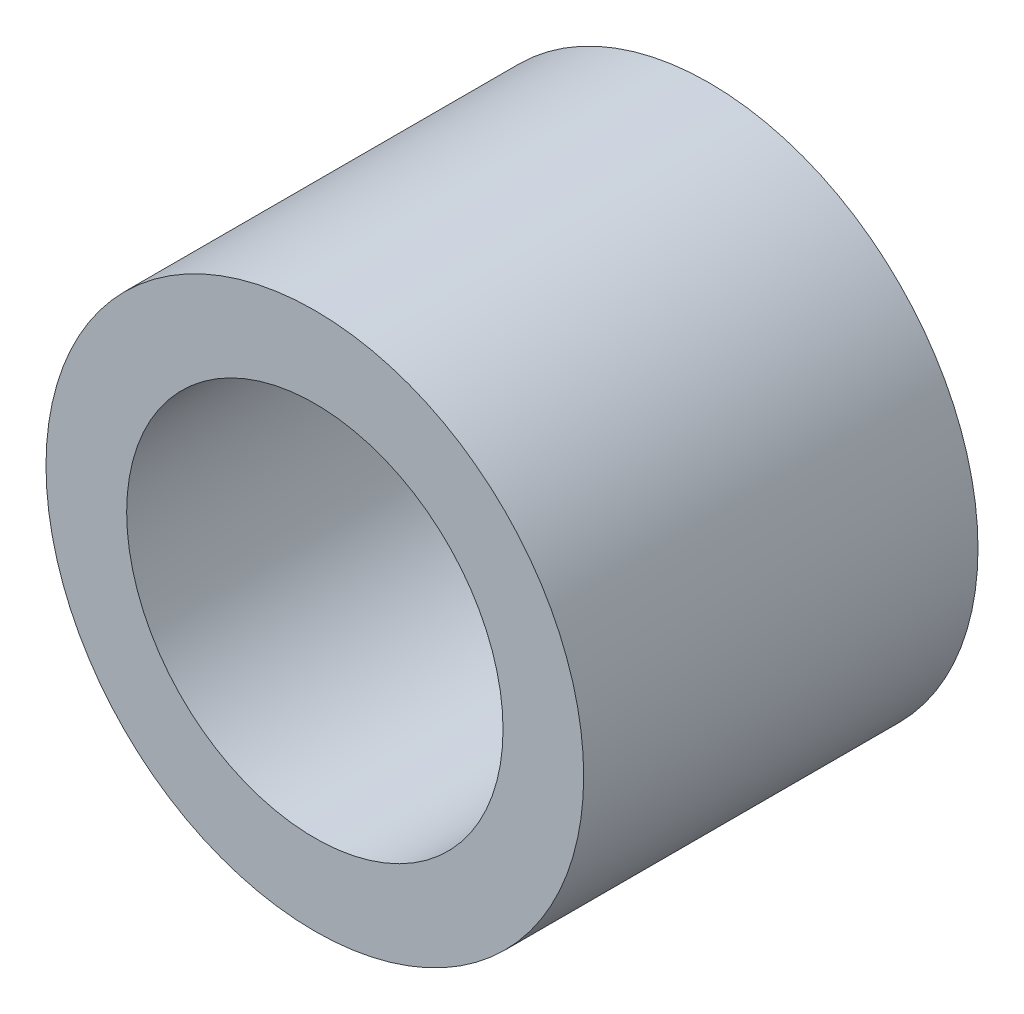
SolidWorks part; units mm, degrees
material "ABS"
ref_plane "Alzado" through (0, 0, 0) normal (0, 0, 1) x (1, 0, 0)
ref_plane "Planta" through (0, 0, 0) normal (0, 1, 0) x (1, 0, 0)
ref_plane "Vista lateral" through (0, 0, 0) normal (1, 0, 0) x (0, 0, -1)
sketch "Croquis1" plane through (0, 0, 0) normal (0, 0, 1) x (1, 0, 0)
  circle A0 centre (0, 0) radius 15
  dimension "D1" = 30
extrude "Saliente-Extruir1" add sketch "Croquis1" along normal blind 22
sketch "Croquis2" plane through (0, 0, 22) normal (0, 0, 1) x (1, 0, 0)
  circle A0 centre (0, 0) radius 10.5
  dimension "D1" = 21
extrude "Cortar-Extruir1" cut sketch "Croquis2" against normal blind 16
sketch "Croquis3" plane through (0, 0, 0) normal (0, 0, -1) x (-1, 0, 0)
  line L0 (0, 0) -> (0, 13.6439) construction
  line L2 (-1.25, 10.4253) -> (-1.25, 9.5)
  line L3 (-1.25, 9.5) -> (1.25, 9.5)
  line L4 (1.25, 10.4253) -> (1.25, 9.5)
  line L5 (8.4036, 6.2952) -> (7.6022, 5.8325)
  line L6 (7.6022, 5.8325) -> (8.8522, 3.6675)
  line L7 (9.6536, 4.1301) -> (8.8522, 3.6675)
  line L8 (9.6536, -4.1301) -> (8.8522, -3.6675)
  line L9 (8.8522, -3.6675) -> (7.6022, -5.8325)
  line L10 (8.4036, -6.2952) -> (7.6022, -5.8325)
  line L11 (1.25, -10.4253) -> (1.25, -9.5)
  line L12 (1.25, -9.5) -> (-1.25, -9.5)
  line L13 (-1.25, -10.4253) -> (-1.25, -9.5)
  line L14 (-8.4036, -6.2952) -> (-7.6022, -5.8325)
  line L15 (-7.6022, -5.8325) -> (-8.8522, -3.6675)
  line L16 (-9.6536, -4.1301) -> (-8.8522, -3.6675)
  line L17 (-9.6536, 4.1301) -> (-8.8522, 3.6675)
  line L18 (-8.8522, 3.6675) -> (-7.6022, 5.8325)
  line L19 (-8.4036, 6.2952) -> (-7.6022, 5.8325)
  circle A0 centre (0, 0) radius 10.5 construction
  circle A1 centre (0, 0) radius 10.5
  point P31 (0, 0)
  dimension "D1" = 21
  dimension "D2" = 2.5
  dimension "D3" = 0.9253
  dimension "D4" = 9.5
  dimension "D5" = 6
extrude "Cortar-Extruir2" cut sketch "Croquis3" against normal blind 1 contours L4 A1 L2 L3 | L19 A1 L17 L18 | L7 A1 L5 L6 | L10 A1 L8 L9 | L13 A1 L11 L12 | L16 A1 L14 L15 region at (0, 9.9878, 0) region at (8.6497, 4.9939, 0) region at (-8.6497, 4.9939, 0) region at (8.6497, -4.9939, 0) region at (-8.6497, -4.9939, 0) region at (0, -9.9878, 0)
sketch "Croquis5" plane through (0, 0, 0) normal (0, 0, -1) x (-1, 0, 0)
  circle A0 centre (0, 0) radius 10.5
  circle A1 centre (0, 0) radius 11
  dimension "D1" = 22
extrude "Cortar-Extruir3" cut sketch "Croquis5" against normal blind 1
sketch "Croquis6" plane through (0, 0, 0) normal (0, 0, -1) x (-1, 0, 0)
  circle A0 centre (0, 0) radius 1.25
  dimension "D1" = 2.5
extrude "Cortar-Extruir4" cut sketch "Croquis6" against normal through all and the other way through all
ref_axis "Eje1" through (0, 0, 6) along (0, 0, -1)
